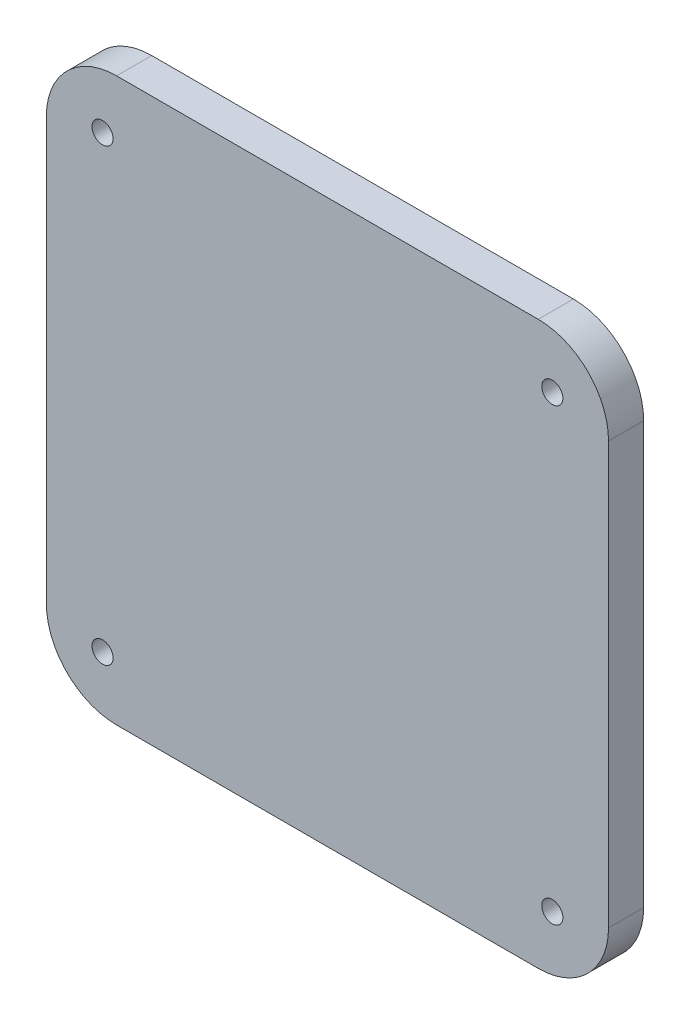
SolidWorks part; units mm, degrees
ref_plane "Plan de face" through (0, 0, 0) normal (0, 0, 1) x (1, 0, 0)
ref_plane "Plan de dessus" through (0, 0, 0) normal (0, 1, 0) x (1, 0, 0)
ref_plane "Plan de droite" through (0, 0, 0) normal (1, 0, 0) x (0, 0, -1)
sketch "Esquisse1" plane through (0, 0, 0) normal (0, 0, 1) x (1, 0, 0)
  line L1 (-40, 40) -> (40, 40)
  line L2 (-40, 40) -> (-40, -40)
  line L3 (-40, -40) -> (40, -40)
  line L4 (40, 40) -> (40, -40)
  circle A0 centre (0, 0) radius 34 construction
  point P4 (0, 40)
  point P5 (-40, 0)
  dimension "D3" = 68
  dimension "D1" = 80
  dimension "D2" = 80
extrude "Boss.-Extru.1" add sketch "Esquisse1" along normal blind 5
sketch "Esquisse2" plane through (0, 0, 5) normal (0, 0, 1) x (1, 0, 0)
  line L0 (-13, 9) -> (-13, 24.7476) construction
  line L1 (-13, 9) -> (-26.976, 9) construction
  circle A0 centre (-13, 9) radius 12
  circle A1 centre (-22.5, 21) radius 0.5
  circle A2 centre (-3.5, 21) radius 0.5
  circle A3 centre (-22.5, -3) radius 0.5
  circle A4 centre (-3.5, -3) radius 0.5
  circle A5 centre (-22.5, 21) radius 3 construction
  dimension "D1" = 19
  dimension "D2" = 24
  dimension "D3" = 1
  dimension "D4" = 24
  dimension "D7" = 6
  dimension "D5" = 13
  dimension "D6" = 9
extrude "xlr" [suppressed] cut sketch "Esquisse2" against normal through all both and the other way through all
sketch "Esquisse3" plane through (0, 0, 5) normal (0, 0, 1) x (1, 0, 0)
  line L0 (19.7073, 8.5) -> (32.9204, 8.5) construction
  line L1 (20, 1) -> (34.7955, 1) construction
  circle A0 centre (20, 16) radius 3.75
  circle A1 centre (0, 0) radius 34 construction
  circle A2 centre (20, 1) radius 3.75
  circle A3 centre (20, -14) radius 3.75
  circle A4 centre (20, 16) radius 6 construction
  circle A5 centre (20, 1) radius 6 construction
  dimension "D1" = 30
  dimension "D3" = 1
  dimension "D4" = 7.5
  dimension "D5" = 12
  dimension "D2" = 20
extrude "banane" [suppressed] cut sketch "Esquisse3" against normal through all both and the other way through all
sketch "Esquisse4" plane through (0, 0, 5) normal (0, 0, 1) x (1, 0, 0)
  circle A0 centre (-1, -20) radius 3.2
  dimension "D1" = 6.4
  dimension "D2" = 20
  dimension "D3" = 1
extrude "RCA" [suppressed] cut sketch "Esquisse4" against normal through all both and the other way through all
fillet "Congé1" radius 10 4 edges at (-40, -40, 2.5) (40, -40, 2.5) (40, 40, 2.5) (-40, 40, 2.5)
sketch "Esquisse5" plane through (0, 0, 5) normal (0, 0, 1) x (1, 0, 0)
  line L0 (0, 0) -> (0, 40) construction
  line L1 (-40, 40) -> (40, 40) construction
  line L2 (0, 0) -> (40, 0) construction
  line L3 (40, 40) -> (40, -40) construction
  line L4 (40, 40) -> (0, 0) construction
  circle A0 centre (32, 32) radius 1.5
  circle A1 centre (-32, 32) radius 1.5
  circle A2 centre (-32, -32) radius 1.5
  circle A3 centre (32, -32) radius 1.5
  dimension "D1" = 64
  dimension "D2" = 3
extrude "Enlèv. mat.-Extru.4" cut sketch "Esquisse5" against normal through all both and the other way through all
